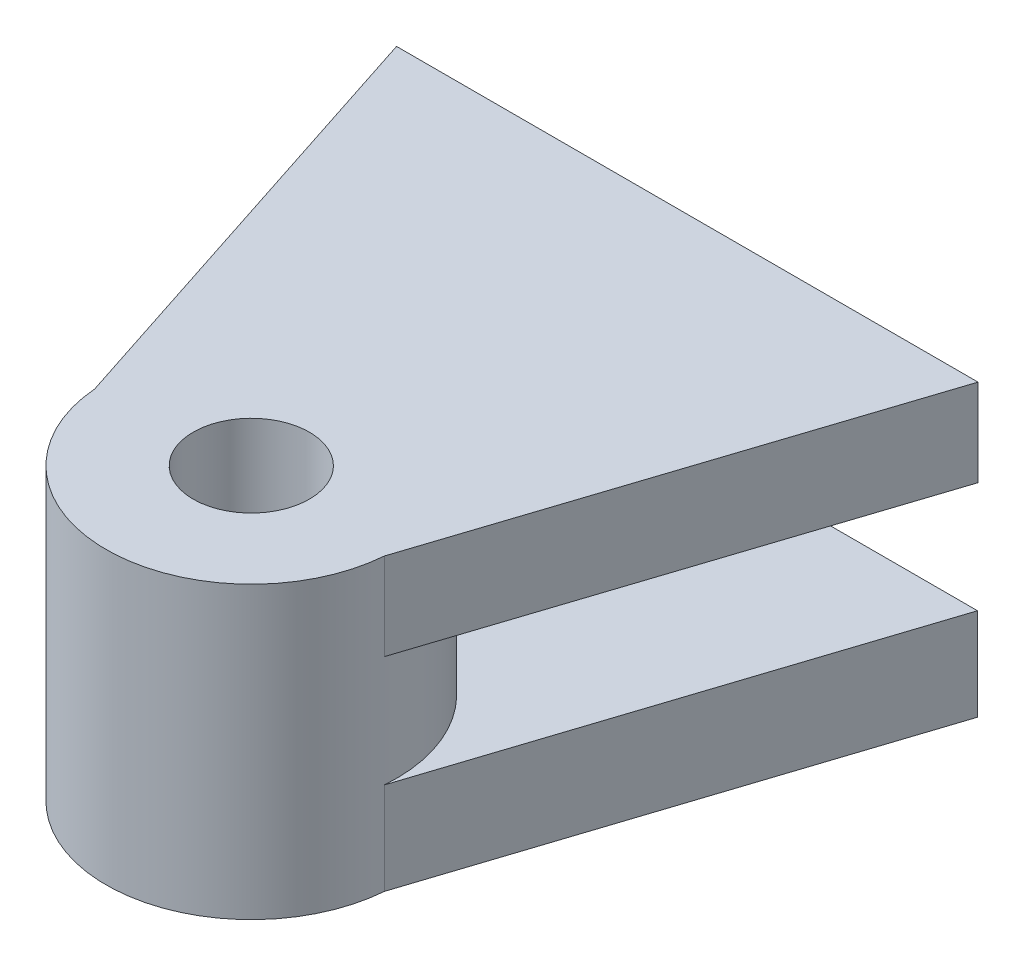
SolidWorks part; units mm, degrees
ref_plane "Front Plane" through (0, 0, 0) normal (0, 0, 1) x (1, 0, 0)
ref_plane "Top Plane" through (0, 0, 0) normal (0, 1, 0) x (1, 0, 0)
ref_plane "Right Plane" through (0, 0, 0) normal (1, 0, 0) x (0, 0, -1)
sketch "Sketch1" plane through (0, 0, 0) normal (0, 1, 0) x (1, 0, 0)
  line L0 (0, 0) -> (40, 0)
  line L4 (0, 0) -> (10.0326, -30.8063)
  line L5 (29.9674, -30.8063) -> (40, 0)
  line L6 (20, 0) -> (20, -17.1488) construction
  line L7 (10.0326, -30.8063) -> (29.9674, -30.8063) construction
  line L8 (5.2585, 0) -> (12.7764, -23.0848)
  circle A0 centre (20, -30) radius 4
  circle A1 centre (20, -30) radius 10
  point P11 (0, 0)
  point P12 (5.2599, 0)
  point P14 (12.794, -23.0665)
  dimension "D2" = 20
  dimension "D3" = 8
  dimension "D1" = 40
  dimension "D4" = 30
  dimension "D5" = 5
extrude "Boss-Extrude1" add sketch "Sketch1" along normal blind 6.35 contours A1 L5 L0 L4 | A1 L8 L0 L4 | A1 | A0 region at (6.7745, 0, 13.0959) region at (22.9519, 0, 10.2837)
extrude "Boss-Extrude2" add sketch "Sketch1<3>" along normal blind 20 contours A1 A0 | A1 L8 L0 L4 region at (6.7745, 0, 13.0959) region at (10.8438, 0, 26.7463)
sketch "Sketch1<3>" plane through (0, 0, 0) normal (0, 1, 0) x (1, 0, 0) same geometry as "Sketch1"
ref_plane "Plane1" through (0, 10, 0) normal (0, 1, 0) x (1, 0, 0)
sketch "Sketch2" plane through (0, 20, 0) normal (0, 1, 0) x (1, 0, 0)
  line L0 (0, 0) -> (40.0342, 0)
  line L1 (5.2585, 0) -> (40, 0) construction
  line L2 (40.0342, 0) -> (29.9674, -30.8063)
  line L3 (29.9674, -30.8063) -> (40, 0) construction
  line L4 (0, 0) -> (10.0326, -30.8063)
  line L5 (0, 0) -> (11.4693, -35.2179) construction
  circle A0 centre (20, -30) radius 10 construction
  circle A1 centre (20, -30) radius 10
  circle A2 centre (20, -30) radius 4
  circle M1 centre (20, -30) radius 4
  arc M2 (10.0326, -30.8063) -> (12.7764, -23.0848) centre (20, -30) ccw
extrude "Boss-Extrude3" add sketch "Sketch2" against normal blind 6 contours L0 L4 L2 M2 | M2 M1 region at (20.0117, 20, 10.7965) region at (10.8438, 20, 26.7463)
equation "\"20.00mm_5\"=20"
